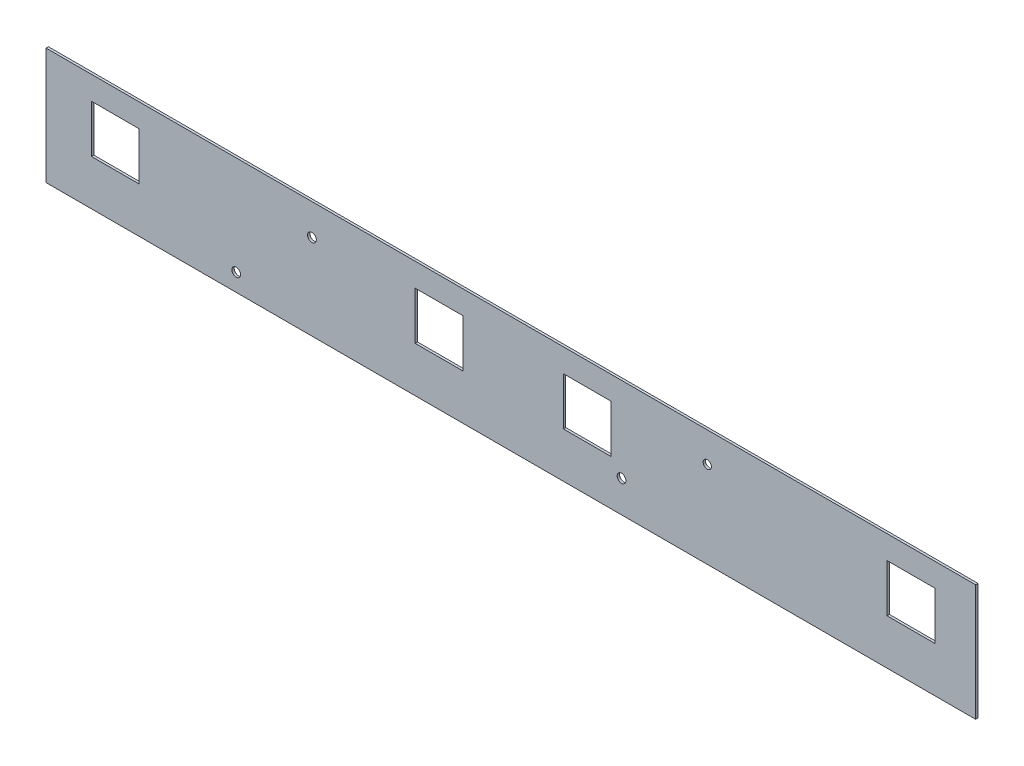
SolidWorks part; units mm, degrees
note: The reader was unsure of these and kept them because the rebuilt part matched: thickness of "Base-Flange1", "Sheet-Metal1", "Sheet-Metal4", "Sheet-Metal5", "Sheet-Metal6".
material "ABS"
ref_plane "X-Y Datum" through (0, 0, 0) normal (0, 0, 1) x (1, 0, 0)
ref_plane "X-Z Datum" through (0, 0, 0) normal (0, 1, 0) x (1, 0, 0)
ref_plane "Y-Z Datum" through (0, 0, 0) normal (1, 0, 0) x (0, 0, -1)
sketch "Sketch1" plane through (0, 0, 0) normal (0, 0, 1) x (1, 0, 0)
  line L0 (-350.637, -168.4194) -> (272.9229, -168.4194)
  line L5 (-350.637, -168.4194) -> (-350.637, -90.2559)
  line L6 (-350.637, -90.2559) -> (272.9229, -90.2559)
  line L7 (272.9229, -168.4194) -> (272.9229, -90.2559)
base flange "Base-Flange1" sketch "Sketch1" thickness 1.5875 reverse thickness direction no parameters "D1"=9.525
sketch "Sketch3" plane through (0, 0, 0) normal (0, 0, 1) x (1, 0, 0)
  line L0 (-317.6499, -135.4524) -> (-290.6499, -135.4524) construction
  line L1 (-317.6499, -135.4524) -> (-317.6499, -108.4524) construction
  line L2 (-317.6499, -108.4524) -> (-290.6499, -108.4524) construction
  line L3 (-290.6499, -135.4524) -> (-290.6499, -108.4524) construction
  line L4 (-317.6499, -135.4524) -> (-290.6499, -108.4524) construction
  line L5 (-317.6499, -108.4524) -> (-290.6499, -135.4524) construction
  line L6 (216.1108, -135.4524) -> (243.1108, -135.4524) construction
  line L7 (216.1108, -135.4524) -> (216.1108, -108.4524) construction
  line L8 (216.1108, -108.4524) -> (243.1108, -108.4524) construction
  line L9 (243.1108, -135.4524) -> (243.1108, -108.4524) construction
  line L10 (216.1108, -135.4524) -> (243.1108, -108.4524) construction
  line L11 (216.1108, -108.4524) -> (243.1108, -135.4524) construction
  line L12 (-1.1075, -135.4524) -> (25.8925, -135.4524) construction
  line L13 (-1.1075, -135.4524) -> (-1.1075, -108.4524) construction
  line L14 (-1.1075, -108.4524) -> (25.8925, -108.4524) construction
  line L15 (25.8925, -135.4524) -> (25.8925, -108.4524) construction
  line L16 (-1.1075, -135.4524) -> (25.8925, -108.4524) construction
  line L17 (-1.1075, -108.4524) -> (25.8925, -135.4524) construction
  line L18 (-100.4316, -135.4524) -> (-73.4316, -135.4524) construction
  line L19 (-100.4316, -135.4524) -> (-100.4316, -108.4524) construction
  line L20 (-100.4316, -108.4524) -> (-73.4316, -108.4524) construction
  line L21 (-73.4316, -135.4524) -> (-73.4316, -108.4524) construction
  line L22 (-100.4316, -135.4524) -> (-73.4316, -108.4524) construction
  line L23 (-100.4316, -108.4524) -> (-73.4316, -135.4524) construction
  line L24 (272.9229, -90.2559) -> (100.0301, -90.2559) construction
  line L25 (272.9229, -90.2559) -> (272.9229, -148.8843) construction
  line L26 (272.9229, -148.8843) -> (100.0301, -148.8843) construction
  line L27 (100.0301, -90.2559) -> (100.0301, -148.8843) construction
  line L28 (-320.1899, -137.9924) -> (-288.1099, -137.9924)
  line L29 (-288.1099, -137.9924) -> (-288.1099, -105.9124)
  line L30 (-320.1899, -105.9124) -> (-288.1099, -105.9124)
  line L31 (-320.1899, -137.9924) -> (-320.1899, -105.9124)
  line L32 (-102.9716, -137.9924) -> (-70.8916, -137.9924)
  line L33 (-70.8916, -137.9924) -> (-70.8916, -105.9124)
  line L34 (-102.9716, -105.9124) -> (-70.8916, -105.9124)
  line L35 (-102.9716, -137.9924) -> (-102.9716, -105.9124)
  line L36 (-3.6475, -137.9924) -> (28.4325, -137.9924)
  line L37 (28.4325, -137.9924) -> (28.4325, -105.9124)
  line L38 (-3.6475, -105.9124) -> (28.4325, -105.9124)
  line L39 (-3.6475, -137.9924) -> (-3.6475, -105.9124)
  line L40 (213.5708, -137.9924) -> (245.6508, -137.9924)
  line L41 (245.6508, -137.9924) -> (245.6508, -105.9124)
  line L42 (213.5708, -105.9124) -> (245.6508, -105.9124)
  line L43 (213.5708, -137.9924) -> (213.5708, -105.9124)
  line L44 (-350.637, -168.4194) -> (272.9229, -168.4194) construction
  line L45 (272.9229, -168.4194) -> (272.9229, -90.2559) construction
  circle A0 centre (92.9145, -110.3691) radius 2.75
  circle A1 centre (35.3919, -147.1475) radius 2.921
  circle A2 centre (-172.2477, -111.061) radius 2.921
  circle A3 centre (-223.0592, -156.6647) radius 2.921
  circle A4 centre (-197.6534, -133.8628) radius 34.1376 construction
  circle A5 centre (64.1532, -128.7583) radius 34.1376 construction
  point P0 (-304.1499, -121.9524)
  point P5 (229.6108, -121.9524)
  point P10 (12.3925, -121.9524)
  point P15 (-86.9316, -121.9524)
  point P32 (272.9229, -90.2559)
  dimension "D2" = 68.2752
  dimension "D3" = 68.2752
  dimension "D4" = 68.2752
  dimension "D1" = 27
  dimension "D5" = 27
  dimension "D6" = 72.3242
  dimension "D7" = 39.6611
  dimension "D8" = 208.7696
  dimension "D9" = 27
  dimension "D10" = 27
  dimension "D11" = 190.2183
  dimension "D12" = 2.54
  dimension "D13" = 2.54
  dimension "D14" = 2.54
  dimension "D15" = 2.54
extrude "Cut-Extrude3" cut sketch "Sketch3" against normal through all normal cut yes
sketch "Sketch4" plane through (0, 0, 0) normal (0, 0, 1) x (1, 0, 0)
  line L0 (272.9229, -90.2559) -> (-38.8571, -90.2559)
  line L1 (272.9229, -90.2559) -> (272.9229, -168.7239)
  line L2 (272.9229, -168.7239) -> (-38.8571, -168.7239)
  line L3 (-38.8571, -90.2559) -> (-38.8571, -168.7239)
  point P4 (272.9229, -90.2559)
extrude "Cut-Extrude4" [suppressed] cut sketch "Sketch4" against normal through all
sketch "Sketch5" plane through (0, 0, 0) normal (0, 0, 1) x (1, 0, 0)
  line L0 (272.9229, -90.2559) -> (-35.6821, -90.2559)
  line L1 (272.9229, -90.2559) -> (272.9229, -168.7239)
  line L2 (272.9229, -168.7239) -> (-35.6821, -168.7239)
  line L3 (-35.6821, -90.2559) -> (-35.6821, -168.7239)
  point P4 (272.9229, -90.2559)
extrude "Cut-Extrude5" [suppressed] cut sketch "Sketch5" against normal through all flip side to cut
sketch "Bend-Lines1" [suppressed] plane through (0, 0, 0) normal (0, 1, 0) x (1, 0, 0)
sketch "Bounding-Box1" [suppressed] plane through (0, 0, 0) normal (0, 1, 0) x (1, 0, 0)
sheet metal parameters "Sheet-Metal1" thickness 1.5875 parameters "D1"=9.525
flat pattern "Flat-Pattern1" [suppressed]
sketch "Bend-Lines2" plane through (0, 0, 0) normal (0, 1, 0) x (1, 0, 0)
sketch3d "Bounding-Box2" [suppressed]
  line L0 (-350.637, -168.4194, 0) -> (272.9229, -168.4194, 0) construction
  line L1 (-350.637, -90.2559, 0) -> (272.9229, -90.2559, 0) construction
  line L2 (-350.637, -168.4194, 0) -> (-350.637, -90.2559, 0) construction
  line L3 (272.9229, -168.4194, 0) -> (272.9229, -90.2559, 0) construction
sheet metal parameters "Sheet-Metal4" thickness 1.5875 parameters "D1"=9.525
flat pattern "Flat-Pattern1"
sketch "Bend-Lines2" plane through (0, 0, 0) normal (0, 1, 0) x (1, 0, 0)
sketch3d "Bounding-Box2" [suppressed]
  line L0 (-350.637, -168.4194, 0) -> (272.9229, -168.4194, 0) construction
  line L1 (-350.637, -90.2559, 0) -> (272.9229, -90.2559, 0) construction
  line L2 (-350.637, -168.4194, 0) -> (-350.637, -90.2559, 0) construction
  line L3 (272.9229, -168.4194, 0) -> (272.9229, -90.2559, 0) construction
sheet metal parameters "Sheet-Metal5" thickness 1.5875 parameters "D1"=9.525
flat pattern "Flat-Pattern1"
sketch "Bend-Lines2" plane through (0, 0, 0) normal (0, 1, 0) x (1, 0, 0)
sketch3d "Bounding-Box2" [suppressed]
  line L0 (-350.637, -168.4194, 0) -> (-38.8571, -168.4194, 0) construction
  line L1 (-350.637, -90.2559, 0) -> (-38.8571, -90.2559, 0) construction
  line L2 (-350.637, -168.4194, 0) -> (-350.637, -90.2559, 0) construction
  line L3 (-38.8571, -168.4194, 0) -> (-38.8571, -90.2559, 0) construction
sheet metal parameters "Sheet-Metal6" thickness 1.5875 parameters "D1"=9.525
flat pattern "Flat-Pattern1"
sketch "Bend-Lines2" plane through (0, 0, 0) normal (0, 1, 0) x (1, 0, 0)
sketch3d "Bounding-Box2" [suppressed]
  line L0 (-35.6821, -168.4194, 0) -> (272.9229, -168.4194, 0) construction
  line L1 (-35.6821, -90.2559, 0) -> (272.9229, -90.2559, 0) construction
  line L2 (-35.6821, -168.4194, 0) -> (-35.6821, -90.2559, 0) construction
  line L3 (272.9229, -168.4194, 0) -> (272.9229, -90.2559, 0) construction
